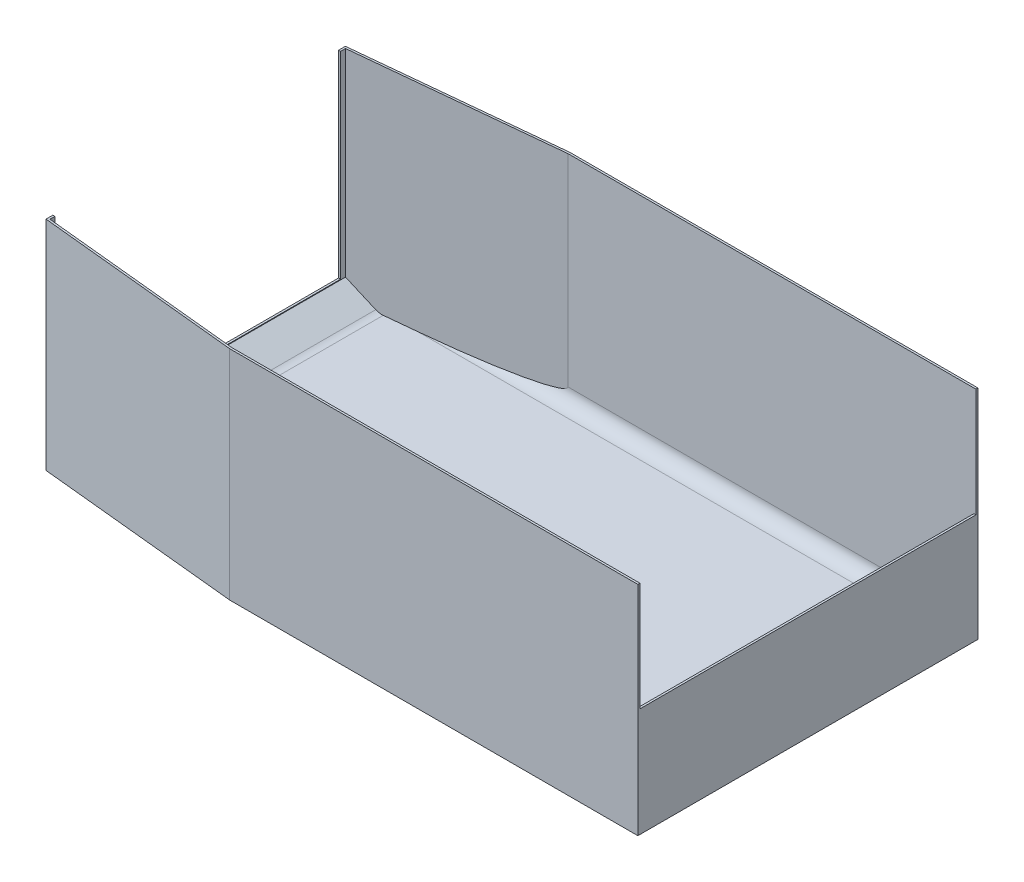
SolidWorks part; units mm, degrees
ref_plane "前视基准面" through (0, 0, 0) normal (0, 0, 1) x (1, 0, 0)
ref_plane "上视基准面" through (0, 0, 0) normal (0, 1, 0) x (1, 0, 0)
ref_plane "右视基准面" through (0, 0, 0) normal (1, 0, 0) x (0, 0, -1)
other "Configuration Table"
sketch "草图1" plane through (0, 0, 0) normal (0, 1, 0) x (1, 0, 0)
  line L0 (0, 0) -> (-300, 0) construction
  line L1 (-150, 125) -> (150, 125)
  line L2 (-150, 125) -> (-150, -125) construction
  line L3 (-150, -125) -> (150, -125)
  line L4 (150, 125) -> (150, -125)
  line L5 (-150, 125) -> (150, -125) construction
  line L6 (-150, -125) -> (150, 125) construction
  line L7 (-300, -110) -> (-300, 110)
  line L8 (-300, 110) -> (-150, 125)
  line L9 (-300, -110) -> (-150, -125)
  point P0 (0, 0)
  point P11 (-300, 0)
  dimension "D1" = 250
  dimension "D2" = 300
  dimension "D3" = 150
  dimension "D4" = 220
extrude "凸台-拉伸1" add sketch "草图1" along normal blind 160
shell "抽壳1" thickness 1.5 removed face at (-100, 160, 0)
sketch "草图2" plane through (-300, 0, 0) normal (-1, 0, 0) x (0, 0, 1)
  line L1 (-105, 200) -> (105, 200)
  line L2 (-105, 200) -> (-105, 15)
  line L3 (-105, 15) -> (105, 15)
  line L4 (105, 200) -> (105, 15)
  line L5 (-110, 0) -> (110, 0) construction
  line L6 (110, 160) -> (110, 0) construction
  line L7 (-110, 160) -> (-110, 0) construction
  dimension "D1" = 15
  dimension "D2" = 5
  dimension "D3" = 5
extrude "切除-拉伸1" cut sketch "草图2" against normal blind 200
chamfer "倒角1" distance 13 angle 60 1 edges at (-298.5, 1.5, 0) first distance on face at (-298.5, 84.125, 0)
sketch "草图6" plane through (150, 0, 0) normal (1, 0, 0) x (0, 0, -1)
  line L0 (-125, 160) -> (125, 160) construction
  line L1 (-123.5, 160) -> (123.5, 160)
  line L2 (-123.5, 160) -> (-123.5, 80)
  line L3 (-123.5, 80) -> (123.5, 80)
  line L4 (123.5, 160) -> (123.5, 80)
  line L5 (125, 160) -> (125, 0) construction
  line L6 (-125, 160) -> (-125, 0) construction
  line L7 (-125, 0) -> (125, 0) construction
  dimension "D1" = 1.5
  dimension "D2" = 1.5
  dimension "D3" = 80
extrude "切除-拉伸2" cut sketch "草图6" against normal blind 200
fillet "圆角1" radius 10 1 edges at (-275.9833, 1.5, 0)
fillet "圆角2" radius 10 2 edges at (-0.7126, 1.5, -123.5) (-0.7126, 1.5, 123.5)
